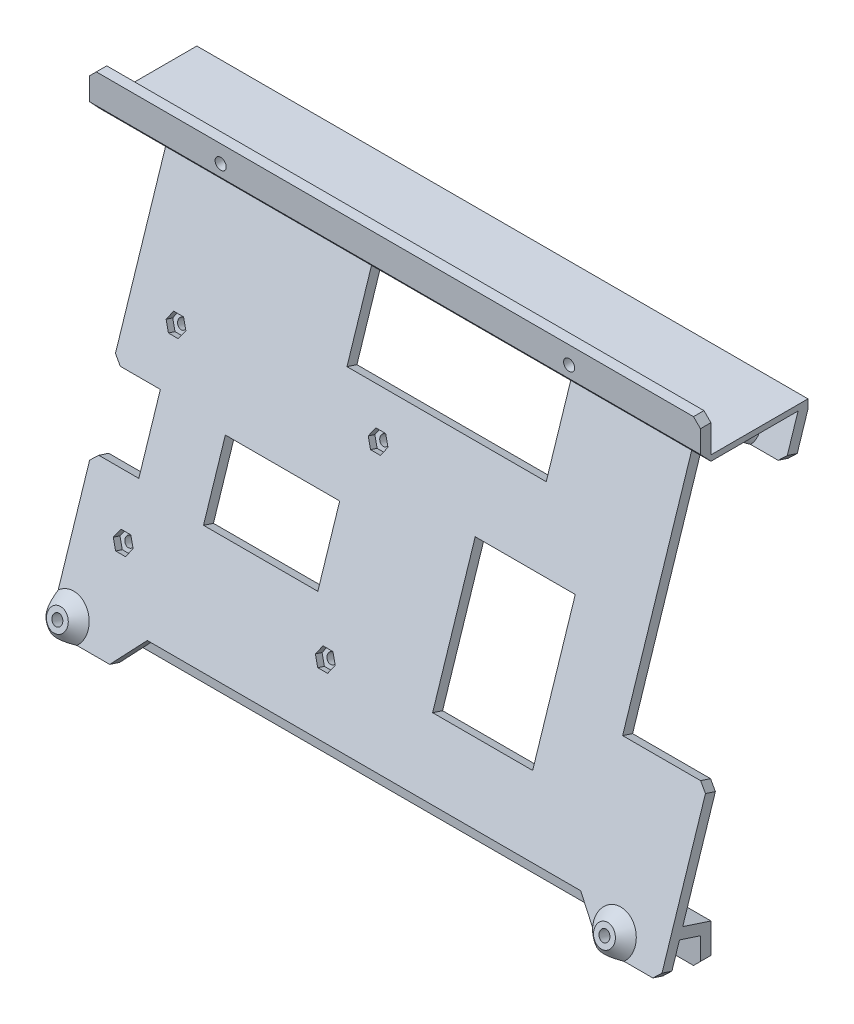
SolidWorks part; units mm, degrees
ref_plane "Alzado" through (0, 0, 0) normal (0, 0, 1) x (1, 0, 0)
ref_plane "Planta" through (0, 0, 0) normal (0, 1, 0) x (1, 0, 0)
ref_plane "Vista lateral" through (0, 0, 0) normal (1, 0, 0) x (0, 0, -1)
sketch "Croquis1" plane through (0, 0, 0) normal (0, 0, 1) x (1, 0, 0)
  line L1 (-89.8, 59.8) -> (89.8, 59.8)
  line L2 (-89.8, 59.8) -> (-89.8, -59.8)
  line L3 (-89.8, -59.8) -> (89.8, -59.8)
  line L4 (89.8, 59.8) -> (89.8, -59.8)
  line L5 (-89.8, 59.8) -> (89.8, -59.8) construction
  line L6 (-89.8, -59.8) -> (89.8, 59.8) construction
  line L7 (-88.2, 58.2) -> (88.2, 58.2)
  line L8 (-88.2, 58.2) -> (-88.2, -58.2)
  line L9 (-88.2, -58.2) -> (88.2, -58.2)
  line L10 (88.2, 58.2) -> (88.2, -58.2)
  line L11 (-88.2, 58.2) -> (88.2, -58.2) construction
  line L12 (-88.2, -58.2) -> (88.2, 58.2) construction
  point P0 (0, 0)
  point P6 (0, 0)
  dimension "D1" = 179.6
  dimension "D2" = 119.6
  dimension "D3" = 1.6
  dimension "D4" = 1.6
sketch "Croquis2" plane through (0, 0, 0) normal (0, 0, 1) x (1, 0, 0)
  line L1 (-100, 68.2) -> (100, 68.2) construction
  line L2 (-100, 68.2) -> (-100, -68.2) construction
  line L3 (-100, -68.2) -> (100, -68.2) construction
  line L4 (100, 68.2) -> (100, -68.2) construction
  line L5 (-100, 68.2) -> (100, -68.2) construction
  line L6 (-100, -68.2) -> (100, 68.2) construction
  line L7 (-88.2, 58.2) -> (88.2, 58.2) construction
  line L8 (-88.2, 58.2) -> (-88.2, -58.2) construction
  line L9 (-88.2, -58.2) -> (88.2, -58.2) construction
  line L10 (88.2, 58.2) -> (88.2, -58.2) construction
  line L11 (-88.2, 58.2) -> (88.2, -58.2) construction
  line L12 (-88.2, -58.2) -> (88.2, 58.2) construction
  line L13 (-87.6833, 59.8) -> (87.6833, 59.8)
  line L14 (-87.6833, 59.8) -> (-87.6833, -59.8) construction
  line L15 (-87.6833, -59.8) -> (87.6833, -59.8) construction
  line L16 (87.6833, 59.8) -> (87.6833, -59.8) construction
  line L17 (-87.6833, 59.8) -> (87.6833, -59.8) construction
  line L18 (-87.6833, -59.8) -> (87.6833, 59.8) construction
  line L21 (0, 0) -> (0, 50000) construction
  line L25 (0, 0) -> (50000, 0) construction
  line L26 (-87.6833, 59.8) -> (-87.6833, 68.2)
  line L27 (87.6833, 59.8) -> (87.6833, 68.2)
  line L28 (87.6833, 68.2) -> (-87.6833, 68.2)
  line L29 (-88.2, -58.2) -> (88.2, -58.2) construction
  line L30 (87.6833, -68.2) -> (-87.6833, -68.2)
  line L31 (87.6833, -59.8) -> (87.6833, -68.2)
  line L32 (-87.6833, -59.8) -> (-87.6833, -68.2)
  line L33 (-87.6833, -59.8) -> (87.6833, -59.8)
  point P1 (0, 0)
  point P6 (0, 0)
  point P14 (0, 0)
  dimension "D1" = 10
  dimension "D2" = 1.6
  dimension "D3" = 200
extrude "Saliente-Extruir2" add sketch "Croquis2" along normal blind 3
sketch "Croquis7" plane through (0, 0, 3) normal (0, 0, 1) x (1, 0, 0)
  line L0 (0, 0) -> (0, 50000) construction
  line L1 (0, 0) -> (50000, 0) construction
  line L2 (0, 63.2) -> (50000, 63.2) construction
  line L7 (87.6833, 68.2) -> (-87.6833, 68.2) construction
  circle A0 centre (0, 63.2) radius 1.6 construction
  circle A2 centre (93.2, 63.2) radius 1.6 construction
  circle A3 centre (93.2, 0) radius 1.6 construction
  circle A4 centre (50, 63.2) radius 1.6
  circle A5 centre (-50, 63.2) radius 1.6
  circle A6 centre (-93.2, 63.2) radius 1.6 construction
  circle A7 centre (-93.2, 0) radius 1.6 construction
  circle A8 centre (50, -63.2) radius 1.6
  circle A9 centre (-50, -63.2) radius 1.6
  dimension "D3" = 3.2
  dimension "D1" = 5
  dimension "D4" = 100
extrude "Cortar-Extruir3" cut sketch "Croquis7" against normal through all
sketch "Croquis8" plane through (87.6833, 0, 0) normal (1, 0, 0) x (0, 0, -1)
  line L0 (0, 0) -> (0, 50000) construction
  line L1 (0, 0) -> (-50000, 0) construction
  line L2 (23.9335, 53.3061) -> (-15426.9162, -47499.5197) construction
  line L3 (25.0038, 56.6) -> (30.2392, 56.6) construction
  line L5 (-8.0992, -54.9888) -> (0, -57.6204)
  line L6 (0, -57.6204) -> (0, -59.8)
  line L7 (0, -59.8) -> (-3, -59.8)
  line L8 (-3, -59.8) -> (-11.8795, -56.9149) construction
  line L9 (-11.8795, -56.9149) -> (25.0038, 56.6)
  line L11 (27.8502, 55.6521) -> (-8.0992, -54.9888)
  line L12 (-11.8795, -56.9149) -> (-14.6606, -65.4744)
  line L13 (-14.6606, -65.4744) -> (-11.8074, -66.4015)
  line L14 (-11.8074, -66.4015) -> (-9.0263, -57.8419)
  line L15 (-9.0263, -57.8419) -> (-3, -59.8)
  line L16 (0, 59.8) -> (50000, 59.8) construction
  line L17 (-18.6587, 58.2) -> (49981.3413, 58.2) construction
  line L19 (0, 58.2) -> (0, 59.8)
  line L20 (0, 59.8) -> (-3, 59.8)
  line L21 (-3, 59.8) -> (0, 56.6)
  line L22 (0, 56.6) -> (25.0038, 56.6)
  line L23 (18.5748, 56.6) -> (15.4281, 56.6) construction
  line L24 (27.8502, 55.6521) -> (27.8502, 58.2)
  line L25 (27.8502, 58.2) -> (0, 58.2)
  dimension "D1" = 18
  dimension "D2" = 3
  dimension "D3" = 3
  dimension "D4" = 9
  dimension "D5" = 23.78
  dimension "D6" = 1.6
  dimension "D7" = 1.6
extrude "Saliente-Extruir3" add sketch "Croquis8" against normal up to surface (175.3666 mm away) up to face at (-87.6833, 64, 1.5)
sketch "Croquis9" plane through (0, -1.9436, -5.9818) normal (0, 0.309, 0.9511) x (1, 0, 0)
  line L0 (0, 0) -> (0, 50000) construction
  line L1 (-83.7, 53.5564) -> (73.3, 53.5564) construction
  line L2 (-83.7, 53.5564) -> (-83.7, -62.4436) construction
  line L3 (-83.7, -62.4436) -> (73.3, -62.4436) construction
  line L4 (73.3, 53.5564) -> (73.3, -62.4436) construction
  line L5 (-83.7, 53.5564) -> (73.3, -62.4436) construction
  line L6 (-83.7, -62.4436) -> (73.3, 53.5564) construction
  circle A0 centre (-83.7, 53.5564) radius 1.5
  circle A1 centre (73.3, 53.5564) radius 1.5
  circle A2 centre (-83.7, -62.4436) radius 1.5
  circle A3 centre (73.3, -62.4436) radius 1.5
  point P0 (-5.2, -4.4436)
  dimension "D4" = 3
  dimension "D1" = 157
  dimension "D2" = 116
  dimension "D3" = 8
  dimension "D5" = 5.2
extrude "Cortar-Extruir4" cut sketch "Croquis9" against normal blind 10
sketch "Croquis10" plane through (0, -1.9436, -5.9818) normal (0, 0.309, 0.9511) x (1, 0, 0)
  circle A0 centre (-83.7, 53.5564) radius 3
  circle A1 centre (73.3, 53.5564) radius 3
  circle A2 centre (73.3, -62.4436) radius 3
  circle A3 centre (-83.7, -62.4436) radius 3
  circle A4 centre (-83.7, 53.5564) radius 1.5
  circle A5 centre (73.3, 53.5564) radius 1.5
  circle A6 centre (73.3, -62.4436) radius 1.5
  circle A7 centre (-83.7, -62.4436) radius 1.5
  dimension "D1" = 6
extrude "Saliente-Extruir4" add sketch "Croquis10" along normal blind 3
sketch "Croquis11" plane through (0, -1.9436, -5.9818) normal (0, 0.309, 0.9511) x (1, 0, 0)
  line L0 (87.6833, 49.5564) -> (63.3, 49.5564)
  line L1 (87.6833, 61.5564) -> (87.6833, -66.8002) construction
  line L2 (63.3, 49.5564) -> (63.3, -22.4436)
  line L3 (63.3, -22.4436) -> (87.6833, -22.4436)
  line L4 (87.6833, -22.4436) -> (87.6833, 49.5564)
  line L5 (0, 0) -> (0, 50000) construction
  line L6 (-68.1198, -57.8002) -> (49931.8802, -57.8002) construction
  line L8 (-62.179, -57.8002) -> (62.179, -57.8002)
  line L9 (62.179, -57.8002) -> (70.177, -66.8002)
  line L10 (-87.6833, -66.8002) -> (87.6833, -66.8002) construction
  line L11 (70.177, -66.8002) -> (-70.177, -66.8002)
  line L12 (-70.177, -66.8002) -> (-62.179, -57.8002)
  line L13 (-87.6833, 61.5564) -> (87.6833, 61.5564) construction
  line L14 (-28.5839, 18.9367) -> (28.5839, 18.9367)
  line L15 (-28.5839, 18.9367) -> (-28.5839, 61.5564)
  line L16 (-28.5839, 61.5564) -> (28.5839, 61.5564)
  line L17 (28.5839, 18.9367) -> (28.5839, 61.5564)
  line L18 (-28.5839, 18.9367) -> (28.5839, 61.5564) construction
  line L19 (-28.5839, 61.5564) -> (28.5839, 18.9367) construction
  line L20 (-87.6833, -57.8002) -> (87.6833, -57.8002) construction
  line L22 (14.0649, 0) -> (42.7738, 0)
  line L23 (14.0649, 0) -> (14.0649, -39.557)
  line L24 (14.0649, -39.557) -> (42.7738, -39.557)
  line L25 (42.7738, 0) -> (42.7738, -39.557)
  line L26 (14.0649, 0) -> (42.7738, -39.557) construction
  line L27 (14.0649, -39.557) -> (42.7738, 0) construction
  line L28 (-55.0414, -8.3874) -> (-22.2313, -8.3874)
  line L29 (-55.0414, -8.3874) -> (-55.0414, -28.6887)
  line L30 (-55.0414, -28.6887) -> (-22.2313, -28.6887)
  line L31 (-22.2313, -8.3874) -> (-22.2313, -28.6887)
  line L32 (-55.0414, -8.3874) -> (-22.2313, -28.6887) construction
  line L33 (-55.0414, -28.6887) -> (-22.2313, -8.3874) construction
  circle A0 centre (73.3, 53.5564) radius 1.5 construction
  circle A1 centre (73.3, -62.4436) radius 1.5 construction
  point P17 (0, -57.8002)
  point P22 (0, 40.2466)
  point P36 (28.4194, -19.7785)
  point P42 (-38.6364, -18.538)
  dimension "D1" = 4
  dimension "D2" = 10
  dimension "D3" = 40
extrude "Cortar-Extruir5" cut sketch "Croquis11" against normal up to next
sketch "Croquis13" plane through (0, -1.9436, -5.9818) normal (0, 0.309, 0.9511) x (1, 0, 0)
  circle A0 centre (-74.1833, 7.6998) radius 1.375
  circle A1 centre (-16.1833, 7.6998) radius 1.375
  circle A2 centre (-74.1833, -41.3002) radius 1.375
  circle A3 centre (-16.1833, -41.3002) radius 1.375
extrude "Cortar-Extruir6" cut sketch "Croquis13" against normal up to next
sketch "Croquis15" plane through (0, -2.8707, -8.835) normal (0, -0.309, -0.9511) x (-1, 0, 0)
  circle A0 centre (16.1833, 7.6998) radius 3
  circle A1 centre (74.1833, 7.6998) radius 3
  circle A2 centre (74.1833, -41.3002) radius 3
  circle A3 centre (16.1833, -41.3002) radius 3
  circle A4 centre (16.1833, -41.3002) radius 1.375 construction
  circle A5 centre (74.1833, -41.3002) radius 1.375 construction
  circle A6 centre (74.1833, 7.6998) radius 1.375 construction
  circle A7 centre (16.1833, 7.6998) radius 1.375 construction
  circle A8 centre (16.1833, -41.3002) radius 1.375
  circle A9 centre (74.1833, -41.3002) radius 1.375
  circle A10 centre (74.1833, 7.6998) radius 1.375
  circle A11 centre (16.1833, 7.6998) radius 1.375
  dimension "D1" = 6
extrude "Saliente-Extruir5" add sketch "Croquis15" along normal blind 3
sketch "Croquis16" plane through (0, -2.8707, -8.835) normal (0, -0.309, -0.9511) x (-1, 0, 0)
  line L0 (16.1833, 7.6998) -> (74.1833, -41.3002) construction
  line L1 (74.1833, -41.3002) -> (16.1833, -41.3002) construction
  line L2 (16.1833, -41.3002) -> (74.1833, 7.6998) construction
  line L3 (74.1833, 7.6998) -> (74.1833, -41.3002) construction
  line L4 (45.1833, -16.8002) -> (50045.1833, -16.8002) construction
  line L5 (87.6833, 61.5345) -> (87.6833, -54.8002) construction
  line L6 (74.1833, -26.8002) -> (87.6833, -26.8002)
  line L7 (74.1833, -26.8002) -> (74.1833, -6.8002)
  line L8 (74.1833, -6.8002) -> (87.6833, -6.8002)
  line L9 (87.6833, -26.8002) -> (87.6833, -6.8002)
  line L10 (74.1833, -26.8002) -> (87.6833, -6.8002) construction
  line L11 (74.1833, -6.8002) -> (87.6833, -26.8002) construction
  point P10 (45.1833, -16.8002)
  point P11 (80.9333, -16.8002)
  dimension "D1" = 20
extrude "Cortar-Extruir8" cut sketch "Croquis16" against normal blind 3
sketch "Croquis17" plane through (0, -1.9436, -5.9818) normal (0, 0.309, 0.9511) x (1, 0, 0)
  line L1 (-71.3427, 7.6998) -> (-72.763, 10.1598)
  line L2 (-72.763, 10.1598) -> (-75.6036, 10.1598)
  line L3 (-75.6036, 10.1598) -> (-77.0238, 7.6998)
  line L4 (-77.0238, 7.6998) -> (-75.6036, 5.2398)
  line L5 (-75.6036, 5.2398) -> (-72.763, 5.2398)
  line L6 (-72.763, 5.2398) -> (-71.3427, 7.6998)
  line L7 (-13.3427, 7.6998) -> (-14.763, 10.1598)
  line L8 (-14.763, 10.1598) -> (-17.6036, 10.1598)
  line L9 (-17.6036, 10.1598) -> (-19.0238, 7.6998)
  line L10 (-19.0238, 7.6998) -> (-17.6036, 5.2398)
  line L11 (-17.6036, 5.2398) -> (-14.763, 5.2398)
  line L12 (-14.763, 5.2398) -> (-13.3427, 7.6998)
  line L13 (-13.3427, -41.3002) -> (-14.763, -38.8402)
  line L14 (-14.763, -38.8402) -> (-17.6036, -38.8402)
  line L15 (-17.6036, -38.8402) -> (-19.0238, -41.3002)
  line L16 (-19.0238, -41.3002) -> (-17.6036, -43.7602)
  line L17 (-17.6036, -43.7602) -> (-14.763, -43.7602)
  line L18 (-14.763, -43.7602) -> (-13.3427, -41.3002)
  line L19 (-71.3427, -41.3002) -> (-72.763, -38.8402)
  line L20 (-72.763, -38.8402) -> (-75.6036, -38.8402)
  line L21 (-75.6036, -38.8402) -> (-77.0238, -41.3002)
  line L22 (-77.0238, -41.3002) -> (-75.6036, -43.7602)
  line L23 (-75.6036, -43.7602) -> (-72.763, -43.7602)
  line L24 (-72.763, -43.7602) -> (-71.3427, -41.3002)
  circle A0 centre (-74.1833, 7.6998) radius 2.46 construction
  circle A1 centre (-16.1833, 7.6998) radius 2.46 construction
  circle A2 centre (-16.1833, -41.3002) radius 2.46 construction
  circle A3 centre (-74.1833, -41.3002) radius 2.46 construction
  dimension "D1" = 4.92
extrude "Cortar-Extruir9" cut sketch "Croquis17" against normal blind 2
chamfer "Chaflán1" distance 2 angle 45 4 edges at (-74.1833, -39.2963, 3.0005) (-16.1833, -39.2963, 3.0005) (-16.1833, 7.3054, -12.1414) (-74.1833, 7.3054, -12.1414)
chamfer "Chaflán2" distance 3 angle 45 4 edges at (73.3, -64.1842, 14.2414) (-83.7, -64.1842, 14.2414) (-83.7, 46.1384, -21.6046) (73.3, 46.1384, -21.6046)
sketch "Croquis18" plane through (0, -2.8707, -8.835) normal (0, -0.309, -0.9511) x (-1, 0, 0)
  line L1 (-70.1246, 53.5564) -> (-71.7123, 56.3064)
  line L2 (-71.7123, 56.3064) -> (-74.8877, 56.3064)
  line L3 (-74.8877, 56.3064) -> (-76.4754, 53.5564)
  line L4 (-76.4754, 53.5564) -> (-74.8877, 50.8064)
  line L5 (-74.8877, 50.8064) -> (-71.7123, 50.8064)
  line L6 (-71.7123, 50.8064) -> (-70.1246, 53.5564)
  line L7 (86.45, 55.1441) -> (83.7, 56.7318)
  line L8 (83.7, 56.7318) -> (80.95, 55.1441)
  line L9 (80.95, 55.1441) -> (80.95, 51.9687)
  line L10 (80.95, 51.9687) -> (83.7, 50.381)
  line L11 (83.7, 50.381) -> (86.45, 51.9687)
  line L12 (86.45, 51.9687) -> (86.45, 55.1441)
  line L13 (86.45, -60.8559) -> (83.7, -59.2682)
  line L14 (83.7, -59.2682) -> (80.95, -60.8559)
  line L15 (80.95, -60.8559) -> (80.95, -64.0313)
  line L16 (80.95, -64.0313) -> (83.7, -65.619)
  line L17 (83.7, -65.619) -> (86.45, -64.0313)
  line L18 (86.45, -64.0313) -> (86.45, -60.8559)
  line L19 (-70.1246, -62.4436) -> (-71.7123, -59.6936)
  line L20 (-71.7123, -59.6936) -> (-74.8877, -59.6936)
  line L21 (-74.8877, -59.6936) -> (-76.4754, -62.4436)
  line L22 (-76.4754, -62.4436) -> (-74.8877, -65.1936)
  line L23 (-74.8877, -65.1936) -> (-71.7123, -65.1936)
  line L24 (-71.7123, -65.1936) -> (-70.1246, -62.4436)
  circle A0 centre (-73.3, 53.5564) radius 2.75 construction
  circle A1 centre (83.7, 53.5564) radius 2.75 construction
  circle A2 centre (83.7, -62.4436) radius 2.75 construction
  circle A3 centre (-73.3, -62.4436) radius 2.75 construction
  dimension "D1" = 5.5
extrude "Cortar-Extruir10" cut sketch "Croquis18" against normal blind 2.5
chamfer "Chaflán3" distance 2 angle 45 10 edges at (87.6833, 68.2, 1.5) (87.6833, 44.7238, -22.7222) (87.6833, -23.7523, -0.4729) (87.6833, -68.2, 1.5) (87.6833, -65.9379, 13.234) (-87.6833, 68.2, 1.5) (-87.6833, -27.8957, 0.8733) (-87.6833, -8.8745, -5.307) (-87.6833, -68.2, 1.5) (-87.6833, -65.923, 13.2801)
